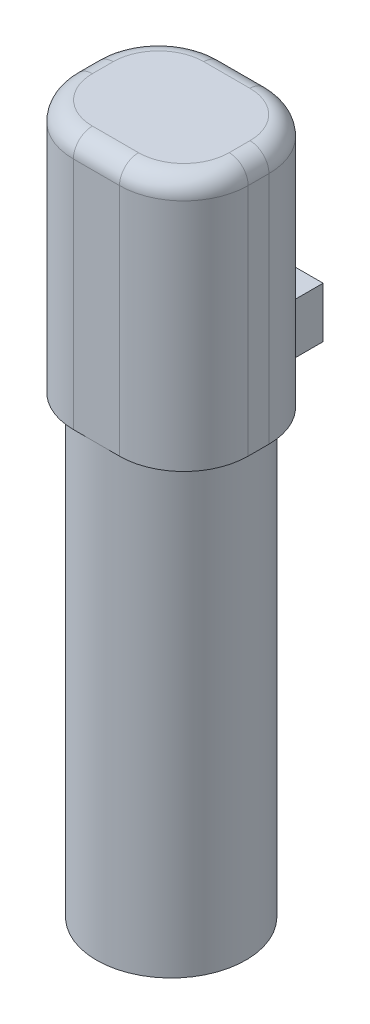
SolidWorks part; units mm, degrees
ref_plane "Front Plane" through (0, 0, 0) normal (0, 0, 1) x (1, 0, 0)
ref_plane "Top Plane" through (0, 0, 0) normal (0, 1, 0) x (1, 0, 0)
ref_plane "Right Plane" through (0, 0, 0) normal (1, 0, 0) x (0, 0, -1)
sketch "Sketch1" plane through (0, 0, 0) normal (0, 1, 0) x (1, 0, 0)
  circle A0 centre (0, 0) radius 2.95
  dimension "D1" = 5.9
extrude "Boss-Extrude1" add sketch "Sketch1" along normal blind 17.686 contours A0
sketch "Sketch2" plane through (0, 0, 0) normal (0, -1, 0) x (1, 0, 0)
  circle A1 centre (0, 0) radius 1.75
  dimension "D1" = 3.5
extrude "Cut-Extrude1" [suppressed] cut sketch "Sketch2" against normal blind 2.5
sketch "Sketch3" plane through (0, 17.686, 0) normal (0, 1, 0) x (1, 0, 0)
  line L1 (-3.45, 2.95) -> (3.45, 2.95)
  line L2 (-3.45, 2.95) -> (-3.45, -2.95)
  line L3 (-3.45, -2.95) -> (3.45, -2.95)
  line L4 (3.45, 2.95) -> (3.45, -2.95)
  line L5 (-3.45, 2.95) -> (3.45, -2.95) construction
  line L6 (-3.45, -2.95) -> (3.45, 2.95) construction
  point P0 (0, 0)
  dimension "D1" = 6.9
  dimension "D2" = 5.9
extrude "Boss-Extrude2" add sketch "Sketch3" along normal blind 10
fillet "Fillet1" radius 2.54 4 edges at (-3.45, 22.686, -2.95) (3.45, 22.686, -2.95) (3.45, 22.686, 2.95) (-3.45, 22.686, 2.95)
fillet "Fillet2" radius 0.75 8 edges at (3.45, 27.686, 0) (2.7061, 27.686, 2.2061) (2.7061, 27.686, -2.2061) (0, 27.686, -2.95) (-2.7061, 27.686, -2.2061) (-3.45, 27.686, 0) (-2.7061, 27.686, 2.2061) (0, 27.686, 2.95)
sketch "Sketch4" plane through (0, 27.686, 0) normal (0, 1, 0) x (1, 0, 0)
  line L0 (0, 2.95) -> (0, -2.95) construction
  line L1 (-0.91, 2.95) -> (0.91, 2.95) construction
  line L2 (0.91, -2.95) -> (-0.91, -2.95) construction
  line L3 (-1.016, 2.95) -> (-1.016, 4.982)
  line L4 (-1.016, 4.982) -> (1.016, 4.982)
  line L5 (1.016, 4.982) -> (1.016, 2.95)
  line L6 (1.016, 2.95) -> (-1.016, 2.95)
  line L7 (0, 4.982) -> (0, 2.95) construction
  dimension "D1" = 2.032
  dimension "D2" = 2.032
extrude "Boss-Extrude3" add sketch "Sketch4" along normal blind 2 from surface starting at face at (2.1204, 17.686, 0)
